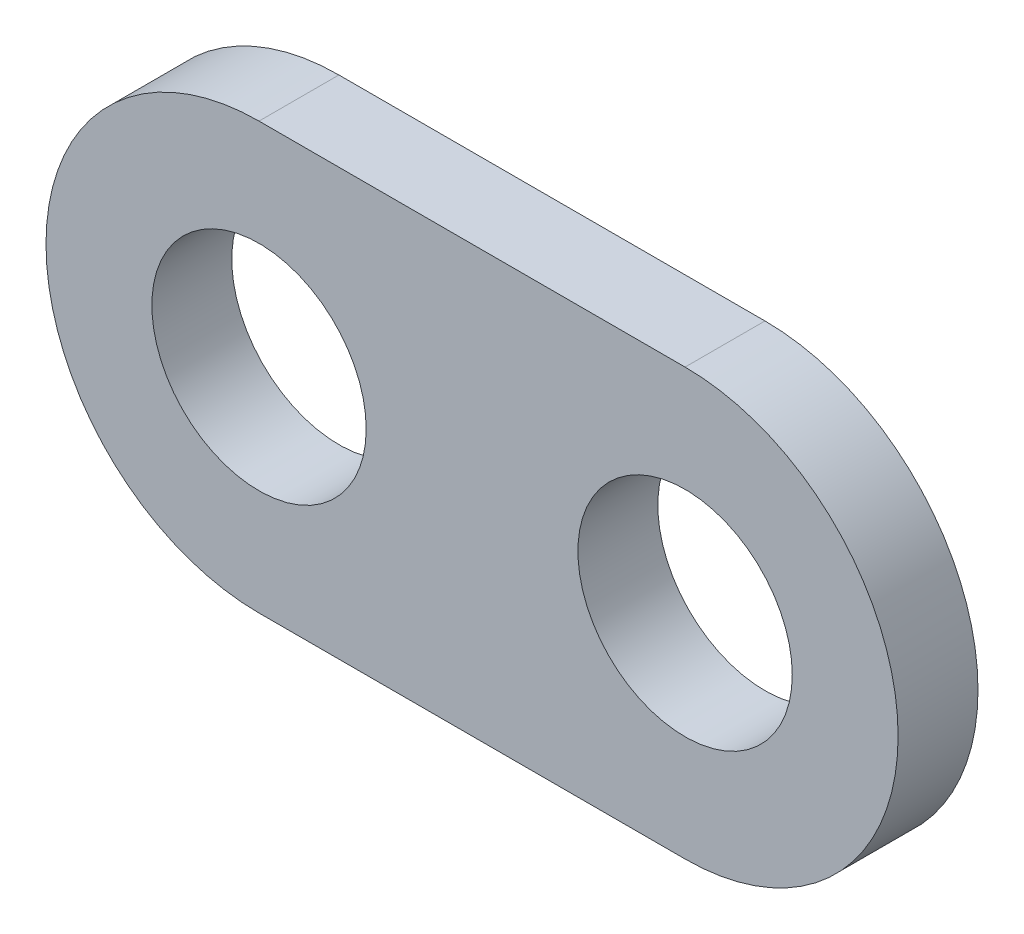
SolidWorks part; units mm, degrees
ref_plane "正面" through (0, 0, 0) normal (0, 0, 1) x (1, 0, 0)
ref_plane "平面" through (0, 0, 0) normal (0, 1, 0) x (1, 0, 0)
ref_plane "右側面" through (0, 0, 0) normal (1, 0, 0) x (0, 0, -1)
sketch "ｽｹｯﾁ1" plane through (0, 0, 0) normal (0, 0, 1) x (1, 0, 0)
  line L6 (8, 38) -> (24, 38) construction
  line L7 (8, 54) -> (24, 54) construction
  line L8 (8, 38) -> (24, 38)
  line L9 (8, 54) -> (24, 54)
  arc A0 (8, 54) -> (8, 38) centre (8, 46) ccw construction
  arc A1 (24, 38) -> (24, 54) centre (24, 46) ccw construction
  arc A4 (8, 54) -> (8, 38) centre (8, 46) ccw
  arc A5 (24, 38) -> (24, 54) centre (24, 46) ccw
  circle A8 centre (8, 46) radius 3.1
  circle A11 centre (8, 46) radius 4.025
  circle A12 centre (24, 46) radius 4.025
  dimension "D1" = 6.2
  dimension "D2" = 8.05
  dimension "D3" = 8.05
extrude "ﾎﾞｽ - 押し出し1" add sketch "ｽｹｯﾁ1" along normal blind 3 from offset 6 contours L8 A5 L9 A4 A12 A11 region at (16, 46, 0)
